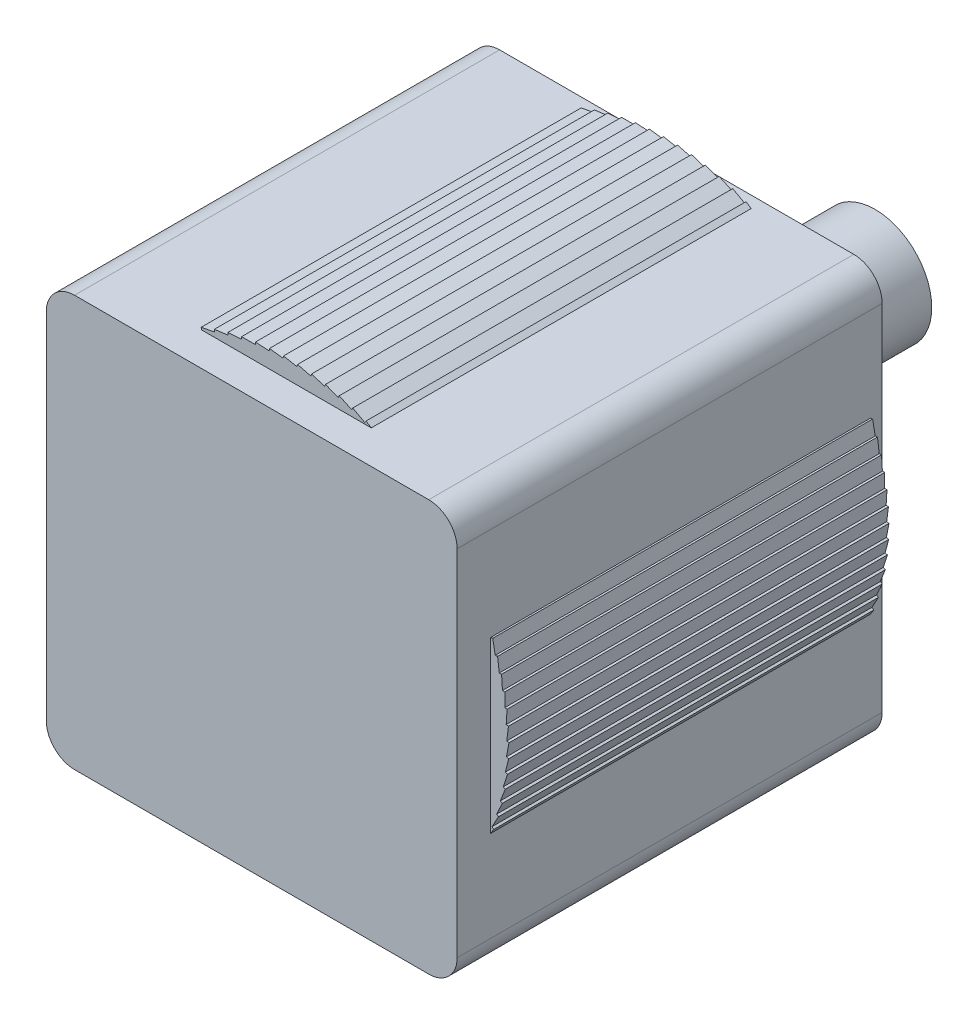
SolidWorks part; units mm, degrees
ref_plane "Front Plane" through (0, 0, 0) normal (0, 0, 1) x (1, 0, 0)
ref_plane "Top Plane" through (0, 0, 0) normal (0, 1, 0) x (1, 0, 0)
ref_plane "Right Plane" through (0, 0, 0) normal (1, 0, 0) x (0, 0, -1)
sketch "Sketch2" plane through (0, 0, 0) normal (0, 0, 1) x (1, 0, 0)
  line L0 (-69.5711, -69.5711) -> (-72.5, -72.5) construction
  line L1 (62.5, -72.5) -> (-62.5, -72.5)
  line L2 (72.5, -62.5) -> (72.5, 62.5)
  line L3 (62.5, 72.5) -> (-62.5, 72.5)
  line L4 (-72.5, -62.5) -> (-72.5, 62.5)
  line L5 (72.5, -72.5) -> (69.5711, -69.5711) construction
  line L6 (72.5, 72.5) -> (69.5711, 69.5711) construction
  line L7 (-69.5711, 69.5711) -> (-72.5, 72.5) construction
  arc A0 (72.5, 62.5) -> (62.5, 72.5) centre (62.5, 62.5) ccw
  arc A1 (62.5, -72.5) -> (72.5, -62.5) centre (62.5, -62.5) ccw
  arc A2 (-62.5, -72.5) -> (-72.5, -62.5) centre (-62.5, -62.5) cw
  arc A3 (-62.5, 72.5) -> (-72.5, 62.5) centre (-62.5, 62.5) ccw
  point P0 (0, 0)
  dimension "D3" = 10
  dimension "D1" = 145
  dimension "D2" = 145
extrude "Boss-Extrude1" add sketch "Sketch2" along normal blind 150
sketch "Sketch3" plane through (0, 0, 0) normal (0, 0, -1) x (-1, 0, 0)
  circle A0 centre (0, 0) radius 20
extrude "Boss-Extrude2" add sketch "Sketch3" along normal blind 70
ref_plane "Plane1" through (0, 77.5, 0) normal (0, -1, 0) x (-1, 0, 0)
sketch "Sketch4" plane through (0, 77.5, 0) normal (0, -1, 0) x (-1, 0, 0)
  line L1 (8.8687, -4.1006) -> (15.3746, -4.1006)
  line L2 (8.8687, -4.1006) -> (8.8687, -138.1898)
  line L3 (8.8687, -138.1898) -> (15.3746, -138.1898)
  line L4 (15.3746, -4.1006) -> (15.3746, -138.1898)
  line L5 (8.8687, -4.1006) -> (15.3746, -138.1898) construction
  line L6 (8.8687, -138.1898) -> (15.3746, -4.1006) construction
  point P0 (12.1216, -71.1452)
extrude "Boss-Extrude3" add sketch "Sketch4" along normal blind 10
pattern_circular "CirPattern1" count 100 over 360 about axis through (0, 0, -70) along (0, 0, 1) of "Boss-Extrude3", "Boss-Extrude2"
